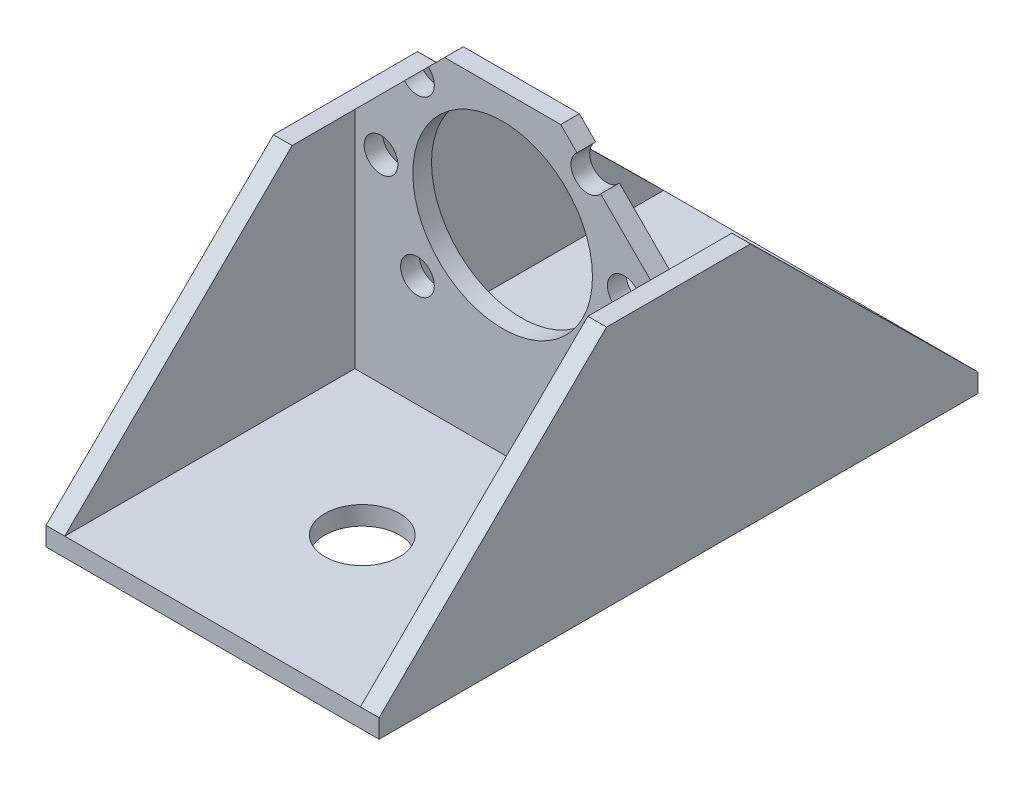
SolidWorks part; units mm, degrees
ref_plane "Alzado" through (0, 0, 0) normal (0, 0, 1) x (1, 0, 0)
ref_plane "Planta" through (0, 0, 0) normal (0, 1, 0) x (1, 0, 0)
ref_plane "Vista lateral" through (0, 0, 0) normal (1, 0, 0) x (0, 0, -1)
sketch "Croquis1" plane through (0, 0, 0) normal (0, 0, 1) x (1, 0, 0)
  line L0 (-19.75, 19.75) -> (19.75, 19.75)
  line L1 (-22.25, -22.25) -> (22.25, -22.25)
  line L2 (-22.25, -22.25) -> (-22.25, 22.25)
  line L3 (-22.25, 22.25) -> (22.25, 22.25)
  line L4 (22.25, -22.25) -> (22.25, 22.25)
  line L5 (-22.25, -22.25) -> (22.25, 22.25) construction
  line L6 (-22.25, 22.25) -> (22.25, -22.25) construction
  line L7 (19.75, -19.75) -> (19.75, 19.75)
  line L8 (-19.75, -19.75) -> (19.75, -19.75)
  line L9 (-19.75, -19.75) -> (-19.75, 19.75)
  point P0 (0, 0)
  dimension "D1" = 44.5
  dimension "D2" = 44.5
  dimension "D3" = 2.5
extrude "Saliente-Extruir1" add sketch "Croquis1" along normal blind 40 and the other way blind 40
sketch "Croquis2" plane through (22.25, 0, 0) normal (1, 0, 0) x (0, 0, -1)
  line L0 (0, 19.75) -> (-40, -19.75)
  line L1 (0, 19.75) -> (40, -19.75)
  line L2 (40, 22.25) -> (-40, 22.25)
  line L3 (-40, 22.25) -> (-40, -19.75)
  line L4 (40, 19.75) -> (-40, 19.75)
  line L5 (-40, 19.75) -> (-40, -19.75)
  line L6 (-40, -19.75) -> (40, -19.75)
  line L7 (40, -19.75) -> (40, 19.75)
  line L8 (40, 19.75) -> (-40, 19.75) construction
  line L9 (-40, 19.75) -> (-40, -19.75)
  line L10 (-40, -19.75) -> (40, -19.75)
  line L11 (40, -19.75) -> (40, 19.75)
  line L12 (40, 22.25) -> (40, -19.75)
  line L13 (-9.6203, 10.25) -> (9.6203, 10.25)
  line M6 (40, 22.25) -> (-40, 22.25)
  line M7 (-40, 22.25) -> (-40, -22.25)
  line M9 (40, -22.25) -> (40, 22.25)
  dimension "D2" = 30
  dimension "D1" = 0
extrude "Cortar-Extruir1" cut sketch "Croquis2" against normal up to surface (44.5 mm away) contours L0 L8 L3 | L8 L1 M9 | L8 M9 M6 M7 | L0 L13 L1 region at (22.25, 13.4167, 0) region at (22.25, 6.5833, -26.6667) region at (22.25, 21, 0) region at (22.25, 6.5833, 26.6667) up to face at (-22.25, 0, 0)
sketch "Croquis3" plane through (0, 0, 0) normal (0, 0, 1) x (1, 0, 0)
  line L0 (19.75, 10.25) -> (19.75, -19.75) construction
  line L1 (-19.75, -19.75) -> (19.75, -19.75) construction
  line L2 (-19.75, -19.75) -> (-19.75, 10.25) construction
  line L3 (19.75, 10.25) -> (19.75, -19.75)
  line L4 (-19.75, -19.75) -> (19.75, -19.75)
  line L5 (-19.75, -19.75) -> (-19.75, 10.25)
  line L6 (19.75, 10.25) -> (-19.75, 10.25)
  line L7 (0, 0) -> (0, 22.25) construction
  line L8 (-7.75, 22.25) -> (7.75, 22.25)
  line L9 (7.75, 22.25) -> (19.75, 10.25)
  line L10 (-7.75, 22.25) -> (-19.75, 10.25)
  dimension "D1" = 12
  dimension "D2" = 45
extrude "Saliente-Extruir2" add sketch "Croquis3" along normal blind 1.25 and the other way blind 1.25 contours L3 L6 L5 L4 | L6 L7 L8 L10 | L7 L6 L9 L8 region at (0, -4.75, 0) region at (7.3114, 15.3773, 0) region at (-7.3114, 15.3773, 0)
sketch "Croquis4" plane through (0, -22.25, 0) normal (0, -1, 0) x (1, 0, 0)
  line L0 (0, 20) -> (0, -20) construction
  circle A0 centre (0, -20) radius 5
  circle A1 centre (0, 20) radius 5
  point P4 (0, 0)
  dimension "D2" = 10
  dimension "D1" = 40
extrude "Cortar-Extruir2" cut sketch "Croquis4" against normal up to surface (2.5 mm away) up to face at (0, -19.75, -20.625)
sketch "Croquis7" plane through (0, 0, 1.25) normal (0, 0, 1) x (1, 0, 0)
  circle A0 centre (0, 6.75) radius 12 construction
  circle A1 centre (0, 6.75) radius 12
extrude "Cortar-Extruir5" cut sketch "Croquis7" against normal up to surface (2.5 mm away) up to face at (0, 4.25, -1.25)
sketch "Croquis8" plane through (0, 0, 1.25) normal (0, 0, 1) x (1, 0, 0)
  line L0 (16.25, 6.75) -> (-16.25, 6.75) construction
  circle A0 centre (-11.3799, 18.35) radius 2.25 construction
  circle A1 centre (11.3799, 18.35) radius 2.25 construction
  circle A2 centre (-11.3799, 18.35) radius 2.25
  circle A3 centre (11.3799, 18.35) radius 2.25
  circle A4 centre (-16.25, 6.75) radius 2.25 construction
  circle A5 centre (-16.25, 6.75) radius 2.25
  circle A6 centre (16.25, 6.75) radius 2.25 construction
  circle A7 centre (16.25, 6.75) radius 2.25
  circle A8 centre (-11.3799, -4.85) radius 2.25
  circle A9 centre (11.3799, -4.85) radius 2.25
extrude "Cortar-Extruir6" cut sketch "Croquis8" against normal up to surface (2.5 mm away) up to face at (12, 6.75, -1.25)
equation "\"D2@Croquis1\"=\"D1@Croquis1\""
